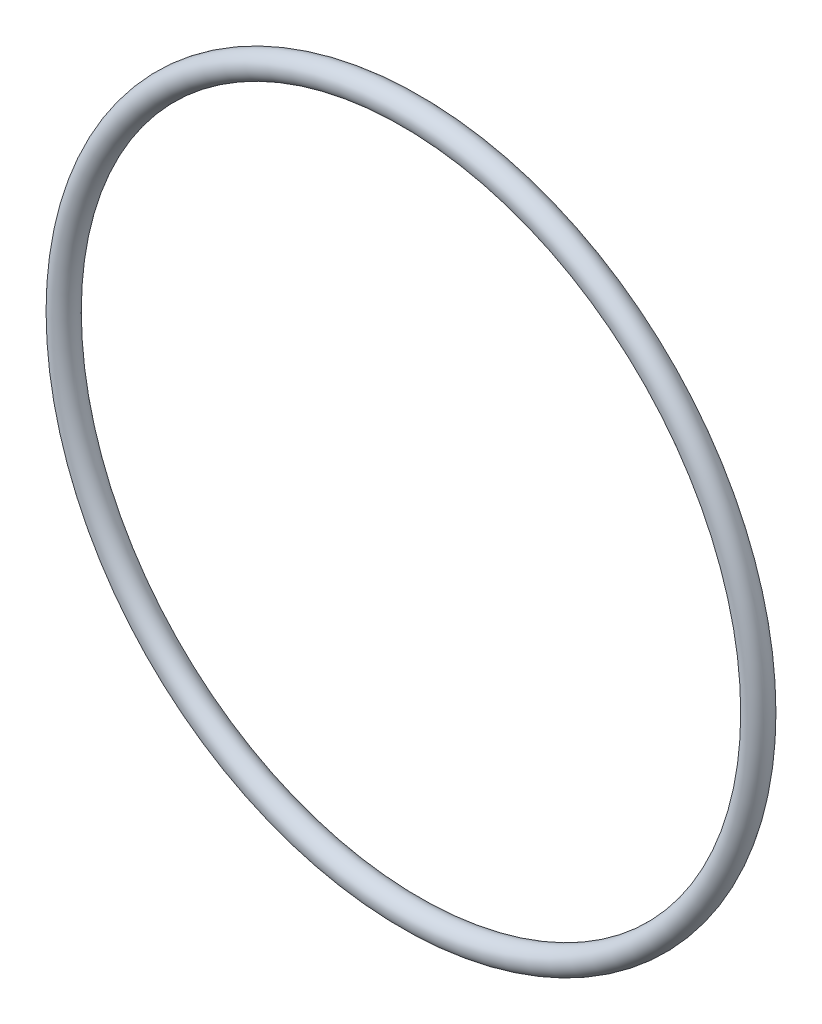
SolidWorks part; units mm, degrees
ref_plane "Front Plane" through (0, 0, 0) normal (0, 0, 1) x (1, 0, 0)
ref_plane "Top Plane" through (0, 0, 0) normal (0, 1, 0) x (1, 0, 0)
ref_plane "Right Plane" through (0, 0, 0) normal (1, 0, 0) x (0, 0, -1)
sketch "Sketch1" plane through (0, 0, 0) normal (0, 0, 1) x (1, 0, 0)
  line L0 (-50.9524, 0) -> (50.9524, 0) construction
  line L1 (-47.4218, 0) -> (47.4218, 0) construction
  line L2 (-36.0288, 36.0288) -> (36.0288, -36.0288) construction
  point P3 (47.4218, 0)
  point P4 (0, 0)
  point P8 (0, 0)
  point P9 (0, 0)
  point P10 (-50.9524, 0)
  point P11 (-47.4218, 0)
  point P14 (0, 0)
  point P15 (36.0288, -36.0288)
  point P16 (50.9524, 0)
  dimension "Actual OD" = 101.9048
  dimension "Actual ID" = 94.8436
  dimension "Actual Width" = 3.5306
  dimension "D1" = 45
sketch "Sketch2" plane through (0, 0, 0) normal (0, 1, 0) x (1, 0, 0)
  line L0 (-50.9524, 0) -> (50.9524, 0) construction
  line L1 (-49.1871, 1.7653) -> (-49.1871, -1.7653) construction
  line L2 (0, -1.7653) -> (0, 1.7653) construction
  circle A0 centre (-49.1871, 0) radius 1.7653
  point P12 (0, 0)
revolve "Revolve1" add sketch "Sketch2" angle 360 about L2
sketch "Sketch3" plane through (0, 0, 0) normal (1, 0, 0) x (0, 0, -1)
  line L0 (-1.7653, 0) -> (1.7653, 0) construction
  line L1 (-1.7653, -35.5663) -> (-1.7653, 35.5663) construction
  point P4 (0, 0)
  point P7 (-1.7653, 0)
  point P9 (-1.7653, -35.5663)
  dimension "D1" = 3.5306
  dimension "D2" = 71.1327
ref_axis "Axis1" through (0, 0, -1.9418) along (0, 0, 1)
equation "\"D1@Sketch3\"=\"Actual Width@Sketch1\""
equation "\"D2@Sketch3\"=\"Actual ID@Sketch1\"*.75"
